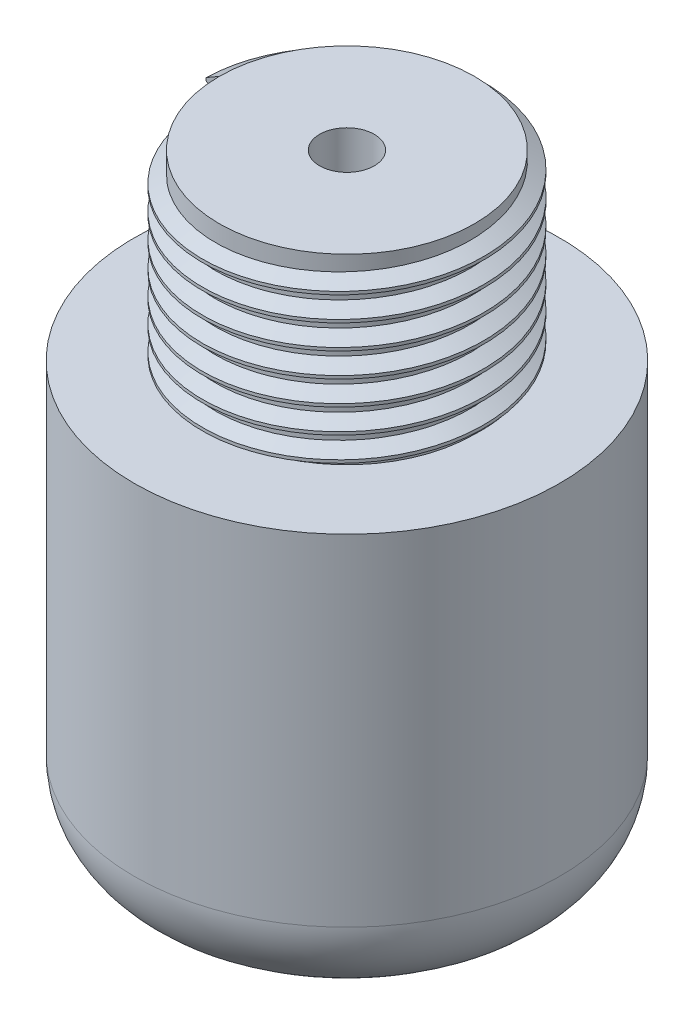
SolidWorks part; units mm, degrees
ref_plane "Front Plane" through (0, 0, 0) normal (0, 0, 1) x (1, 0, 0)
ref_plane "Top Plane" through (0, 0, 0) normal (0, 1, 0) x (1, 0, 0)
ref_plane "Right Plane" through (0, 0, 0) normal (1, 0, 0) x (0, 0, -1)
sketch "Sketch1" plane through (0, 0, 0) normal (0, 1, 0) x (1, 0, 0)
  circle A0 centre (0, 0) radius 17.5
  dimension "D1" = 35
extrude "Boss-Extrude1" add sketch "Sketch1" along normal blind 50
sketch "Sketch2" plane through (0, 0, 0) normal (0, -1, 0) x (1, 0, 0)
  circle A0 centre (0, 0) radius 5
  dimension "D1" = 10
extrude "Cut-Extrude1" cut sketch "Sketch2" against normal blind 25
thread "Thread1" pitch 1.25 method extrude profile "Thread Profile1" start angle 0, offset 0, length 22, pitch 1.25, diameter 10
ref_plane "Plane1" through (5, 0, 0) normal (0, 0, 1) x (1, 0, 0)
sketch "Thread Profile1" plane through (5, 0, 0) normal (0, 0, 1) x (1, 0, 0)
  line L0 (0, 0) -> (0, 1.25) construction
  line L11 (0, 0) -> (0, 1.0937)
  line L12 (0, 1.0937) -> (-0.6766, 0.7031)
  line L13 (-0.6766, 0.7031) -> (-0.6766, 0.3906)
  line L15 (-0.6766, 0.3906) -> (0, 0)
  line L17 (-0.6766, 0.5469) -> (0, 0.5469) construction
  point P2 (0, 0)
  dimension "Pitch" = 1.25
  dimension "Profile_Angle" = 60
  dimension "Profile_Land" = 0.3125
  dimension "Profile_Height" = 0.6766
fillet "Fillet1" radius 7 1 edges at (0, 0, 17.5)
sketch "Sketch6" plane through (0, 50, 0) normal (0, 1, 0) x (1, 0, 0)
  circle A0 centre (0, 0) radius 10.5
  dimension "D1" = 21
extrude "Cut-Extrude2" cut sketch "Sketch6" against normal blind 15 flip side to cut
thread "Thread2" pitch 2 method extrude profile "Thread Profile2" start angle 0, offset 0, length 15, pitch 2, diameter 21
ref_plane "Plane2" through (-10.5, 50, 0) normal (0, 0, 1) x (-1, 0, 0)
sketch "Thread Profile2" plane through (-10.5, 50, 0) normal (0, 0, 1) x (-1, 0, 0)
  line L0 (0, 0) -> (0, 2) construction
  line L1 (0, 0) -> (1.0825, 0.625)
  line L2 (1.0825, 0.625) -> (1.0825, 0.875)
  line L3 (1.0825, 0.875) -> (0, 1.5)
  line L4 (1.0825, 0.75) -> (0, 0.75) construction
  line L11 (0, 0) -> (0, 1.5)
  point P2 (0, 0)
  dimension "Pitch" = 2
  dimension "Profile_Angle" = 60
  dimension "Profile_Land" = 0.25
  dimension "Profile_Height" = 1.0825
sketch "Sketch11" plane through (0, 50, 0) normal (0, 1, 0) x (1, 0, 0)
  circle A0 centre (0, 0) radius 2.25
  dimension "D1" = 4.5
extrude "Cut-Extrude3" cut sketch "Sketch11" against normal blind 3.2
